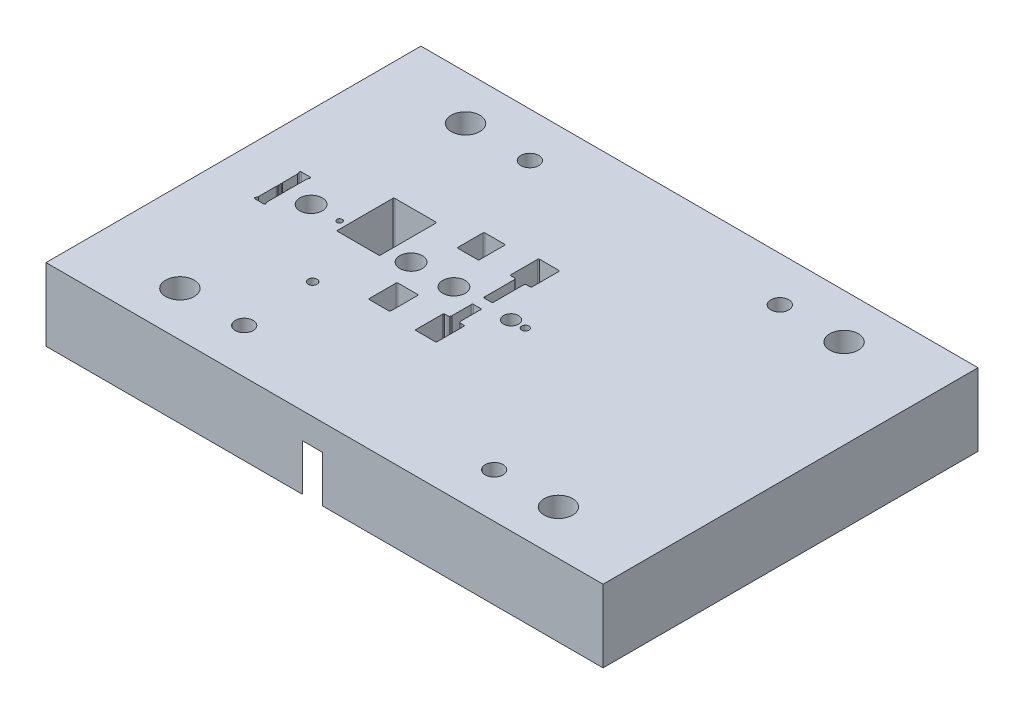
SolidWorks part; units mm, degrees
ref_plane "Front" through (0, 0, 0) normal (0, 0, 1) x (1, 0, 0)
ref_plane "Top" through (0, 0, 0) normal (0, 1, 0) x (1, 0, 0)
ref_plane "Right" through (0, 0, 0) normal (1, 0, 0) x (0, 0, -1)
sketch "Sketch1" plane through (0, 0, 0) normal (0, 0, 1) x (1, 0, 0)
  line L1 (-78, 0) -> (78, 0)
  line L2 (-78, 0) -> (-78, 20.3)
  line L3 (-78, 20.3) -> (78, 20.3)
  line L4 (78, 0) -> (78, 20.3)
  dimension "D1" = 78
  dimension "D2" = 20.3
  dimension "D3" = 78
extrude "Extrude1" add sketch "Sketch1" along normal mid plane 105
hole_wizard "M6 Tapped Hole1" positions "Sketch3" profile "Sketch2" tap size "M6" standard "ISO" end condition through all
sketch "Sketch3" plane through (0, 20.3, 0) normal (0, 1, 0) x (-1, 0, 0)
  point P1 (35, -40)
  point P4 (-35, -40)
  point P13 (-35, 40)
  point P16 (35, 40)
sketch "Sketch2" plane through (-35, 20.3, -40) normal (1, 0, 0) x (0, 0, 1)
  line L0 (0, 0) -> (0, 20.3)
  line L1 (0, 20.3) -> (2.5, 20.3)
  line L2 (2.5, 20.3) -> (2.5, 0)
  line L5 (2.5, 0) -> (0, 0)
  line L11 (0, -6.35) -> (0, 107.95) construction
  dimension "Thru Tap Drill Dia." = 5
  dimension "Thru Tap Drill Depth" = 20.3
cosmetic thread "Hole Thread1" parameters "D2"=6
cosmetic thread "Hole Thread2" parameters "D2"=6
cosmetic thread "Hole Thread5" parameters "D2"=6
cosmetic thread "Hole Thread6" parameters "D2"=6
hole_wizard "Hole1" positions "Sketch5" profile "Sketch4" legacy end condition through all
sketch "Sketch5" plane through (0, 20.3, 0) normal (0, 1, 0) x (-1, 0, 0)
  point P1 (53, -40)
  point P4 (53, 40)
  point P7 (-53, -40)
  point P10 (-53, 40)
sketch "Sketch4" plane through (-53, 20.3, -40) normal (1, 0, 0) x (0, 0, 1)
  line L0 (0, 0) -> (0, 20.3)
  line L1 (0, 20.3) -> (4, 20.3)
  line L2 (4, 20.3) -> (4, 0)
  line L3 (4, 0) -> (0, 0)
  line L4 (0, 110) -> (0, -10) construction
  dimension "Diameter" = 8
  dimension "Depth" = 20.3
hole_wizard "Hole2" positions "Sketch7" profile "Sketch6" legacy
sketch "Sketch7" plane through (0, 0, 0) normal (0, -1, 0) x (1, 0, 0)
  point P0 (14, 14.65)
  point P3 (5, 12.15)
  point P6 (5, -12.1677)
  point P8 (14, -14.65)
  point P11 (35, -12.15)
  point P14 (35, 12.15)
  point P17 (44, 14.65)
  point P20 (44, -14.65)
sketch "Sketch6" plane through (14, 0, 14.65) normal (1, 0, 0) x (0, 0, -1)
  line L0 (0, 0) -> (0, 4.4)
  line L1 (0, 4.4) -> (3.5, 4.4)
  line L2 (3.5, 4.4) -> (3.5, 0)
  line L3 (3.5, 0) -> (0, 0)
  line L4 (0, 110) -> (0, -10) construction
  dimension "Diameter" = 7
  dimension "Depth" = 4.4
sketch "Sketch8" plane through (0, 0, 0) normal (0, -1, 0) x (1, 0, 0)
  line L0 (-78, 52.5) -> (-78, -52.5) construction
  line L1 (-78, 23) -> (-49, 23)
  line L2 (-78, 23) -> (-78, 5)
  line L3 (-78, 5) -> (-49, 5)
  line L4 (-46, 20) -> (-46, 8)
  line L5 (-75.2525, 6) -> (-50.7475, 6) construction
  line L6 (-78, -1) -> (-49, -1)
  line L7 (-78, -1) -> (-78, -21)
  line L8 (-78, -21) -> (-49, -21)
  line L9 (-46, -4) -> (-46, -18)
  line L10 (-78, 22) -> (-48, 22) construction
  line L11 (-76.6263, -2) -> (-49.3737, -2) construction
  line L13 (-78, -20) -> (-48, -20) construction
  line L14 (-48, 11) -> (-48, 22) construction
  arc A0 (-49, -21) -> (-46, -18) centre (-49, -18) ccw
  arc A1 (-49, -1) -> (-46, -4) centre (-49, -4) cw
  arc A2 (-49, 5) -> (-46, 8) centre (-49, 8) ccw
  arc A3 (-49, 23) -> (-46, 20) centre (-49, 20) cw
  dimension "D6" = 3
  dimension "D1" = 1
  dimension "D2" = 1
  dimension "D3" = 1
  dimension "D4" = 1
  dimension "D5" = 2
extrude "Cut-Extrude1" cut sketch "Sketch8" against normal blind 5
sketch "Sketch9" plane through (0, 20.3, 0) normal (0, 1, 0) x (1, 0, 0)
  line L0 (-9.965, 17.15) -> (-9.965, 9.65)
  line L1 (-9.7, 9.385) -> (-8.5894, 9.385)
  line L2 (-8.3917, 9.2771) -> (-8.3123, 9.1537)
  line L3 (-8.275, 9.0266) -> (-8.275, 0.7046)
  line L4 (-18.25, -8.1954) -> (-23.75, -8.1954)
  line L5 (-24, -8.4454) -> (-24, -15.9454)
  line L6 (-23.75, -16.1954) -> (-18.25, -16.1954)
  line L7 (-18, -15.9454) -> (-18, -8.4454)
  line L8 (-18.25, -8.1954) -> (-23.75, -8.1954) construction
  line L9 (-24, -8.4454) -> (-24, -15.9454) construction
  line L10 (-23.75, -16.1954) -> (-18.25, -16.1954) construction
  line L11 (-18, -15.9454) -> (-18, -8.4454) construction
  line L12 (-24, 15.9) -> (-24, 8.9)
  line L13 (-23.75, 8.65) -> (-18.25, 8.65)
  line L14 (-18, 8.9) -> (-18, 15.9)
  line L15 (-18.25, 16.15) -> (-23.75, 16.15)
  line L16 (-24, 15.9) -> (-24, 8.9) construction
  line L17 (-23.75, 8.65) -> (-18.25, 8.65) construction
  line L18 (-18, 8.9) -> (-18, 15.9) construction
  line L19 (-18.25, 16.15) -> (-23.75, 16.15) construction
  line L20 (-33.25, 11.9046) -> (-44.75, 11.9046)
  line L21 (-33, -3.8454) -> (-33, 11.6546)
  line L22 (-44.75, -4.0954) -> (-33.25, -4.0954)
  line L23 (-45, 11.6546) -> (-45, -3.8454)
  line L24 (-33.25, 11.9046) -> (-44.75, 11.9046) construction
  line L25 (-33, -3.8454) -> (-33, 11.6546) construction
  line L26 (-44.75, -4.0954) -> (-33.25, -4.0954) construction
  line L27 (-45, 11.6546) -> (-45, -3.8454) construction
  line L28 (-8.2892, 0.6243) -> (-8.299, 0.5972)
  line L29 (-8.05, 0.2416) -> (-5.95, 0.2416)
  line L30 (-63, -1.2694) -> (-60.1263, -1.2694) construction
  line L31 (-61.75, -6.7884) -> (-61.5151, -7.4339) construction
  line L32 (-64.25, -6.7884) -> (-64.4849, -7.4339) construction
  line L33 (-61.735, -6.7858) -> (-61.501, -7.4288)
  line L34 (-61.75, -7.7844) -> (-64.25, -7.7844)
  line L35 (-64.265, -6.7858) -> (-64.499, -7.4288)
  line L36 (-9, -9.1754) -> (-9.7, -9.1754)
  line L37 (-9.95, -9.4254) -> (-9.95, -16.9254)
  line L38 (-9.7, -17.1754) -> (-4.3, -17.1754)
  line L39 (-4.05, -16.9254) -> (-4.05, -9.4254)
  line L40 (-4.3, -9.1754) -> (-5, -9.1754)
  line L41 (-5.6073, -8.9669) -> (-5.7285, -8.582)
  line L42 (-5.74, -8.5069) -> (-5.74, -3.2709)
  line L43 (-5.7249, -3.1854) -> (-5.7051, -3.1309)
  line L44 (-5.94, -2.7954) -> (-8.06, -2.7954)
  line L45 (-8.2949, -3.1309) -> (-8.2751, -3.1854)
  line L46 (-8.26, -3.2709) -> (-8.26, -8.5069)
  line L47 (-8.2715, -8.582) -> (-8.3927, -8.9669)
  line L48 (-9, -9.1754) -> (-9.7, -9.1754) construction
  line L49 (-9.95, -9.4254) -> (-9.95, -16.9254) construction
  line L50 (-9.7, -17.1754) -> (-4.3, -17.1754) construction
  line L51 (-4.05, -16.9254) -> (-4.05, -9.4254) construction
  line L52 (-4.3, -9.1754) -> (-5, -9.1754) construction
  line L53 (-5.6073, -8.9669) -> (-5.7285, -8.582) construction
  line L54 (-5.74, -8.5069) -> (-5.74, -3.2709) construction
  line L55 (-5.7249, -3.1854) -> (-5.7051, -3.1309) construction
  line L56 (-5.94, -2.7954) -> (-8.06, -2.7954) construction
  line L57 (-8.2949, -3.1309) -> (-8.2751, -3.1854) construction
  line L58 (-8.26, -3.2709) -> (-8.26, -8.5069) construction
  line L59 (-8.2715, -8.582) -> (-8.3927, -8.9669) construction
  line L60 (-9.95, 17.15) -> (-9.95, 9.65)
  line L61 (-9.7, 9.4) -> (-8.5894, 9.4)
  line L62 (-8.3791, 9.2852) -> (-8.2997, 9.1618)
  line L63 (-8.26, 9.0266) -> (-8.26, 0.7046)
  line L64 (-8.2751, 0.6191) -> (-8.2849, 0.5921)
  line L65 (-8.05, 0.2566) -> (-5.95, 0.2566)
  line L66 (-5.7151, 0.5921) -> (-5.7249, 0.6191)
  line L67 (-5.74, 0.7046) -> (-5.74, 9.0266)
  line L68 (-5.7003, 9.1618) -> (-5.6209, 9.2852)
  line L69 (-5.4106, 9.4) -> (-4.3, 9.4)
  line L70 (-4.05, 9.65) -> (-4.05, 17.15)
  line L71 (-4.3, 17.4) -> (-9.7, 17.4)
  line L72 (-9.95, 17.15) -> (-9.95, 9.65) construction
  line L73 (-9.7, 9.4) -> (-8.5894, 9.4) construction
  line L74 (-8.3791, 9.2852) -> (-8.2997, 9.1618) construction
  line L75 (-8.26, 9.0266) -> (-8.26, 0.7046) construction
  line L76 (-8.2751, 0.6191) -> (-8.2849, 0.5921) construction
  line L77 (-8.05, 0.2566) -> (-5.95, 0.2566) construction
  line L78 (-5.7151, 0.5921) -> (-5.7249, 0.6191) construction
  line L79 (-5.74, 0.7046) -> (-5.74, 9.0266) construction
  line L80 (-5.7003, 9.1618) -> (-5.6209, 9.2852) construction
  line L81 (-5.4106, 9.4) -> (-4.3, 9.4) construction
  line L82 (-4.05, 9.65) -> (-4.05, 17.15) construction
  line L83 (-4.3, 17.4) -> (-9.7, 17.4) construction
  line L84 (-64.265, -1.7954) -> (-64.265, -6.7858)
  line L85 (-64.265, 4.247) -> (-64.265, 0.0046)
  line L86 (-64.265, 4.247) -> (-64.499, 4.89)
  line L87 (-64.25, 5.2456) -> (-61.75, 5.2456)
  line L88 (-61.735, 4.247) -> (-61.501, 4.89)
  line L89 (-61.735, 0.0046) -> (-61.735, 4.247)
  line L90 (-5.701, 0.5972) -> (-5.7108, 0.6243)
  line L91 (-5.725, 0.7046) -> (-5.725, 9.0266)
  line L92 (-5.6877, 9.1537) -> (-5.6083, 9.2771)
  line L93 (-5.4106, 9.385) -> (-4.3, 9.385)
  line L94 (-4.035, 9.65) -> (-4.035, 17.15)
  line L95 (-4.3, 17.415) -> (-9.7, 17.415)
  line L96 (-61.735, -6.7858) -> (-61.735, -1.7954)
  line L114 (-64.25, 7.2306) -> (-64.25, 0.0046) construction
  line L115 (-61.75, 0.0046) -> (-61.75, 7.2306) construction
  line L116 (-64.25, -1.7954) -> (-64.25, -9.7694) construction
  line L117 (-61.75, -9.7694) -> (-61.75, -1.7954) construction
  line L118 (-61.75, -7.7694) -> (-64.25, -7.7694) construction
  line L119 (-64.25, 5.2306) -> (-61.75, 5.2306) construction
  line L120 (-64.25, 4.2497) -> (-64.25, 0.0046) construction
  line L121 (-61.75, 0.0046) -> (-61.75, 4.2497) construction
  line L122 (-64.25, -1.7954) -> (-64.25, -6.7884) construction
  line L123 (-61.75, -6.7884) -> (-61.75, -1.7954) construction
  line L124 (-61.75, -7.7694) -> (-64.25, -7.7694) construction
  line L125 (-64.25, 5.2306) -> (-61.75, 5.2306) construction
  line L126 (-64.25, 4.2497) -> (-64.4849, 4.8951) construction
  line L127 (-64.25, 3.4217) -> (-61.75, 3.4217) construction
  line L128 (-63, 3.4217) -> (-63, 4.4835) construction
  line L129 (-61.75, 4.2497) -> (-61.5151, 4.8951) construction
  line L130 (-63, -7.7694) -> (-63, 5.2306) construction
  line L138 (-9, -9.1604) -> (-9.7, -9.1604)
  line L139 (-9.965, -9.4254) -> (-9.965, -16.9254)
  line L140 (-9.7, -17.1904) -> (-4.3, -17.1904)
  line L141 (-4.035, -16.9254) -> (-4.035, -9.4254)
  line L142 (-4.3, -9.1604) -> (-5, -9.1604)
  line L143 (-5.593, -8.9624) -> (-5.7142, -8.5775)
  line L144 (-5.725, -8.5069) -> (-5.725, -3.2709)
  line L145 (-5.7108, -3.1905) -> (-5.691, -3.136)
  line L146 (-5.94, -2.7804) -> (-8.06, -2.7804)
  line L147 (-8.309, -3.136) -> (-8.2892, -3.1905)
  line L148 (-8.275, -3.2709) -> (-8.275, -8.5069)
  line L149 (-8.2858, -8.5775) -> (-8.407, -8.9624)
  line L150 (-24.015, 15.9) -> (-24.015, 8.9)
  line L151 (-23.75, 8.635) -> (-18.25, 8.635)
  line L152 (-17.985, 8.9) -> (-17.985, 15.9)
  line L153 (-18.25, 16.165) -> (-23.75, 16.165)
  line L154 (-18.25, -8.1804) -> (-23.75, -8.1804)
  line L155 (-24.015, -8.4454) -> (-24.015, -15.9454)
  line L156 (-23.75, -16.2104) -> (-18.25, -16.2104)
  line L157 (-17.985, -15.9454) -> (-17.985, -8.4454)
  line L158 (-33.25, 11.9196) -> (-44.75, 11.9196)
  line L159 (-45.015, 11.6546) -> (-45.015, -3.8454)
  line L160 (-44.75, -4.1104) -> (-33.25, -4.1104)
  line L161 (-32.985, -3.8454) -> (-32.985, 11.6546)
  arc A0 (-9.965, 9.65) -> (-9.7, 9.385) centre (-9.7, 9.65) ccw
  arc A1 (-8.3917, 9.2771) -> (-8.5894, 9.385) centre (-8.5894, 9.15) ccw
  arc A2 (-8.275, 9.0266) -> (-8.3123, 9.1537) centre (-8.51, 9.0266) ccw
  arc A3 (-8.2892, 0.6243) -> (-8.275, 0.7046) centre (-8.51, 0.7046) ccw
  arc A4 (-23.75, -8.1954) -> (-24, -8.4454) centre (-23.75, -8.4454) ccw
  arc A5 (-24, -15.9454) -> (-23.75, -16.1954) centre (-23.75, -15.9454) ccw
  arc A6 (-18.25, -16.1954) -> (-18, -15.9454) centre (-18.25, -15.9454) ccw
  arc A7 (-18, -8.4454) -> (-18.25, -8.1954) centre (-18.25, -8.4454) ccw
  arc A8 (-23.75, -8.1954) -> (-24, -8.4454) centre (-23.75, -8.4454) ccw construction
  arc A9 (-24, -15.9454) -> (-23.75, -16.1954) centre (-23.75, -15.9454) ccw construction
  arc A10 (-18.25, -16.1954) -> (-18, -15.9454) centre (-18.25, -15.9454) ccw construction
  arc A11 (-18, -8.4454) -> (-18.25, -8.1954) centre (-18.25, -8.4454) ccw construction
  arc A12 (-24, 8.9) -> (-23.75, 8.65) centre (-23.75, 8.9) ccw
  arc A13 (-18.25, 8.65) -> (-18, 8.9) centre (-18.25, 8.9) ccw
  arc A14 (-18, 15.9) -> (-18.25, 16.15) centre (-18.25, 15.9) ccw
  arc A15 (-23.75, 16.15) -> (-24, 15.9) centre (-23.75, 15.9) ccw
  arc A16 (-24, 8.9) -> (-23.75, 8.65) centre (-23.75, 8.9) ccw construction
  arc A17 (-18.25, 8.65) -> (-18, 8.9) centre (-18.25, 8.9) ccw construction
  arc A18 (-18, 15.9) -> (-18.25, 16.15) centre (-18.25, 15.9) ccw construction
  arc A19 (-23.75, 16.15) -> (-24, 15.9) centre (-23.75, 15.9) ccw construction
  arc A20 (-33, 11.6546) -> (-33.25, 11.9046) centre (-33.25, 11.6546) ccw
  arc A21 (-33.25, -4.0954) -> (-33, -3.8454) centre (-33.25, -3.8454) ccw
  arc A22 (-45, -3.8454) -> (-44.75, -4.0954) centre (-44.75, -3.8454) ccw
  arc A23 (-44.75, 11.9046) -> (-45, 11.6546) centre (-44.75, 11.6546) ccw
  arc A24 (-33, 11.6546) -> (-33.25, 11.9046) centre (-33.25, 11.6546) ccw construction
  arc A25 (-33.25, -4.0954) -> (-33, -3.8454) centre (-33.25, -3.8454) ccw construction
  arc A26 (-45, -3.8454) -> (-44.75, -4.0954) centre (-44.75, -3.8454) ccw construction
  arc A27 (-44.75, 11.9046) -> (-45, 11.6546) centre (-44.75, 11.6546) ccw construction
  arc A28 (-8.299, 0.5972) -> (-8.05, 0.2416) centre (-8.05, 0.5066) ccw
  arc A29 (-5.95, 0.2416) -> (-5.701, 0.5972) centre (-5.95, 0.5066) ccw
  arc A30 (-5.725, 0.7046) -> (-5.7108, 0.6243) centre (-5.49, 0.7046) ccw
  arc A31 (-5.6877, 9.1537) -> (-5.725, 9.0266) centre (-5.49, 9.0266) ccw
  arc A32 (-5.4106, 9.385) -> (-5.6083, 9.2771) centre (-5.4106, 9.15) ccw
  arc A33 (-4.3, 9.385) -> (-4.035, 9.65) centre (-4.3, 9.65) ccw
  arc A34 (-4.035, 17.15) -> (-4.3, 17.415) centre (-4.3, 17.15) ccw
  arc A35 (-9.7, 17.415) -> (-9.965, 17.15) centre (-9.7, 17.15) ccw
  arc A36 (-9.95, 9.65) -> (-9.7, 9.4) centre (-9.7, 9.65) ccw
  arc A37 (-8.3791, 9.2852) -> (-8.5894, 9.4) centre (-8.5894, 9.15) ccw
  arc A38 (-8.26, 9.0266) -> (-8.2997, 9.1618) centre (-8.51, 9.0266) ccw
  arc A39 (-8.2751, 0.6191) -> (-8.26, 0.7046) centre (-8.51, 0.7046) ccw
  arc A40 (-8.5194, -9.0963) -> (-8.4688, -9.0707) centre (-8.5835, -8.9068) ccw
  arc A41 (-9, -9.1754) -> (-8.5194, -9.0963) centre (-9, -7.6754) ccw
  arc A42 (-9.7, -9.1754) -> (-9.95, -9.4254) centre (-9.7, -9.4254) ccw
  arc A43 (-9.95, -16.9254) -> (-9.7, -17.1754) centre (-9.7, -16.9254) ccw
  arc A44 (-4.3, -17.1754) -> (-4.05, -16.9254) centre (-4.3, -16.9254) ccw
  arc A45 (-4.05, -9.4254) -> (-4.3, -9.1754) centre (-4.3, -9.4254) ccw
  arc A46 (-5.4806, -9.0963) -> (-5, -9.1754) centre (-5, -7.6754) ccw
  arc A47 (-5.5312, -9.0707) -> (-5.4806, -9.0963) centre (-5.4165, -8.9068) ccw
  arc A48 (-5.6073, -8.9669) -> (-5.5312, -9.0707) centre (-5.4165, -8.9068) ccw
  arc A49 (-5.74, -8.5069) -> (-5.7285, -8.582) centre (-5.49, -8.5069) ccw
  arc A50 (-5.7249, -3.1854) -> (-5.74, -3.2709) centre (-5.49, -3.2709) ccw
  arc A51 (-5.7051, -3.1309) -> (-5.94, -2.7954) centre (-5.94, -3.0454) ccw
  arc A52 (-8.06, -2.7954) -> (-8.2949, -3.1309) centre (-8.06, -3.0454) ccw
  arc A53 (-8.26, -3.2709) -> (-8.2751, -3.1854) centre (-8.51, -3.2709) ccw
  arc A54 (-8.2715, -8.582) -> (-8.26, -8.5069) centre (-8.51, -8.5069) ccw
  arc A55 (-8.4688, -9.0707) -> (-8.3927, -8.9669) centre (-8.5835, -8.9068) ccw
  arc A56 (-8.5194, -9.0963) -> (-8.4688, -9.0707) centre (-8.5835, -8.9068) ccw construction
  arc A57 (-9, -9.1754) -> (-8.5194, -9.0963) centre (-9, -7.6754) ccw construction
  arc A58 (-9.7, -9.1754) -> (-9.95, -9.4254) centre (-9.7, -9.4254) ccw construction
  arc A59 (-9.95, -16.9254) -> (-9.7, -17.1754) centre (-9.7, -16.9254) ccw construction
  arc A60 (-4.3, -17.1754) -> (-4.05, -16.9254) centre (-4.3, -16.9254) ccw construction
  arc A61 (-4.05, -9.4254) -> (-4.3, -9.1754) centre (-4.3, -9.4254) ccw construction
  arc A62 (-5.4806, -9.0963) -> (-5, -9.1754) centre (-5, -7.6754) ccw construction
  arc A63 (-5.5312, -9.0707) -> (-5.4806, -9.0963) centre (-5.4165, -8.9068) ccw construction
  arc A64 (-5.6073, -8.9669) -> (-5.5312, -9.0707) centre (-5.4165, -8.9068) ccw construction
  arc A65 (-5.74, -8.5069) -> (-5.7285, -8.582) centre (-5.49, -8.5069) ccw construction
  arc A66 (-5.7249, -3.1854) -> (-5.74, -3.2709) centre (-5.49, -3.2709) ccw construction
  arc A67 (-5.7051, -3.1309) -> (-5.94, -2.7954) centre (-5.94, -3.0454) ccw construction
  arc A68 (-8.06, -2.7954) -> (-8.2949, -3.1309) centre (-8.06, -3.0454) ccw construction
  arc A69 (-8.26, -3.2709) -> (-8.2751, -3.1854) centre (-8.51, -3.2709) ccw construction
  arc A70 (-8.2715, -8.582) -> (-8.26, -8.5069) centre (-8.51, -8.5069) ccw construction
  arc A71 (-8.4688, -9.0707) -> (-8.3927, -8.9669) centre (-8.5835, -8.9068) ccw construction
  arc A72 (-8.2849, 0.5921) -> (-8.05, 0.2566) centre (-8.05, 0.5066) ccw
  arc A73 (-5.95, 0.2566) -> (-5.7151, 0.5921) centre (-5.95, 0.5066) ccw
  arc A74 (-5.74, 0.7046) -> (-5.7249, 0.6191) centre (-5.49, 0.7046) ccw
  arc A75 (-5.7003, 9.1618) -> (-5.74, 9.0266) centre (-5.49, 9.0266) ccw
  arc A76 (-5.4106, 9.4) -> (-5.6209, 9.2852) centre (-5.4106, 9.15) ccw
  arc A77 (-4.3, 9.4) -> (-4.05, 9.65) centre (-4.3, 9.65) ccw
  arc A78 (-4.05, 17.15) -> (-4.3, 17.4) centre (-4.3, 17.15) ccw
  arc A79 (-9.7, 17.4) -> (-9.95, 17.15) centre (-9.7, 17.15) ccw
  arc A80 (-9.95, 9.65) -> (-9.7, 9.4) centre (-9.7, 9.65) ccw construction
  arc A81 (-8.3791, 9.2852) -> (-8.5894, 9.4) centre (-8.5894, 9.15) ccw construction
  arc A82 (-8.26, 9.0266) -> (-8.2997, 9.1618) centre (-8.51, 9.0266) ccw construction
  arc A83 (-8.2751, 0.6191) -> (-8.26, 0.7046) centre (-8.51, 0.7046) ccw construction
  arc A84 (-8.2849, 0.5921) -> (-8.05, 0.2566) centre (-8.05, 0.5066) ccw construction
  arc A85 (-5.95, 0.2566) -> (-5.7151, 0.5921) centre (-5.95, 0.5066) ccw construction
  arc A86 (-5.74, 0.7046) -> (-5.7249, 0.6191) centre (-5.49, 0.7046) ccw construction
  arc A87 (-5.7003, 9.1618) -> (-5.74, 9.0266) centre (-5.49, 9.0266) ccw construction
  arc A88 (-5.4106, 9.4) -> (-5.6209, 9.2852) centre (-5.4106, 9.15) ccw construction
  arc A89 (-4.3, 9.4) -> (-4.05, 9.65) centre (-4.3, 9.65) ccw construction
  arc A90 (-4.05, 17.15) -> (-4.3, 17.4) centre (-4.3, 17.15) ccw construction
  arc A91 (-9.7, 17.4) -> (-9.95, 17.15) centre (-9.7, 17.15) ccw construction
  arc A92 (-61.5151, -7.4339) -> (-61.75, -7.7694) centre (-61.75, -7.5194) cw construction
  arc A93 (-64.4849, -7.4339) -> (-64.25, -7.7694) centre (-64.25, -7.5194) ccw construction
  arc A94 (-61.501, -7.4288) -> (-61.75, -7.7844) centre (-61.75, -7.5194) cw
  arc A95 (-64.499, -7.4288) -> (-64.25, -7.7844) centre (-64.25, -7.5194) ccw
  arc A96 (-64.212, -1.6364) -> (-64.265, -1.7954) centre (-64, -1.7954) ccw
  arc A97 (-64.212, -1.6364) -> (-64.212, -1.3544) centre (-64.4, -1.4954) ccw
  arc A98 (-64.212, -1.0364) -> (-64.212, -1.3544) centre (-64, -1.1954) ccw
  arc A99 (-64.212, -1.0364) -> (-64.212, -0.7544) centre (-64.4, -0.8954) ccw
  arc A100 (-64.212, -0.4364) -> (-64.212, -0.7544) centre (-64, -0.5954) ccw
  arc A101 (-64.212, -0.4364) -> (-64.212, -0.1544) centre (-64.4, -0.2954) ccw
  arc A102 (-64.265, 0.0046) -> (-64.212, -0.1544) centre (-64, 0.0046) ccw
  arc A103 (-64.499, 4.89) -> (-64.25, 5.2456) centre (-64.25, 4.9806) cw
  arc A104 (-61.501, 4.89) -> (-61.75, 5.2456) centre (-61.75, 4.9806) ccw
  arc A105 (-61.788, -0.1544) -> (-61.735, 0.0046) centre (-62, 0.0046) ccw
  arc A106 (-61.788, -0.1544) -> (-61.788, -0.4364) centre (-61.6, -0.2954) ccw
  arc A107 (-61.788, -0.7544) -> (-61.788, -0.4364) centre (-62, -0.5954) ccw
  arc A108 (-61.788, -0.7544) -> (-61.788, -1.0364) centre (-61.6, -0.8954) ccw
  arc A109 (-61.788, -1.3544) -> (-61.788, -1.0364) centre (-62, -1.1954) ccw
  arc A110 (-61.788, -1.3544) -> (-61.788, -1.6364) centre (-61.6, -1.4954) ccw
  arc A111 (-61.735, -1.7954) -> (-61.788, -1.6364) centre (-62, -1.7954) ccw
  arc A132 (-61.8, -0.1454) -> (-61.75, 0.0046) centre (-62, 0.0046) ccw construction
  arc A133 (-61.8, -0.1454) -> (-61.8, -0.4454) centre (-61.6, -0.2954) ccw construction
  arc A134 (-61.8, -0.7454) -> (-61.8, -0.4454) centre (-62, -0.5954) ccw construction
  arc A135 (-61.8, -0.7454) -> (-61.8, -1.0454) centre (-61.6, -0.8954) ccw construction
  arc A136 (-61.8, -1.3454) -> (-61.8, -1.0454) centre (-62, -1.1954) ccw construction
  arc A137 (-61.8, -1.3454) -> (-61.8, -1.6454) centre (-61.6, -1.4954) ccw construction
  arc A138 (-61.75, -1.7954) -> (-61.8, -1.6454) centre (-62, -1.7954) ccw construction
  arc A139 (-61.8, -0.1454) -> (-61.75, 0.0046) centre (-62, 0.0046) ccw construction
  arc A140 (-61.8, -0.1454) -> (-61.8, -0.4454) centre (-61.6, -0.2954) ccw construction
  arc A141 (-61.8, -0.7454) -> (-61.8, -0.4454) centre (-62, -0.5954) ccw construction
  arc A142 (-61.8, -0.7454) -> (-61.8, -1.0454) centre (-61.6, -0.8954) ccw construction
  arc A143 (-61.8, -1.3454) -> (-61.8, -1.0454) centre (-62, -1.1954) ccw construction
  arc A144 (-61.8, -1.3454) -> (-61.8, -1.6454) centre (-61.6, -1.4954) ccw construction
  arc A145 (-61.75, -1.7954) -> (-61.8, -1.6454) centre (-62, -1.7954) ccw construction
  arc A146 (-64.25, 0.0046) -> (-64.2, -0.1454) centre (-64, 0.0046) ccw construction
  arc A147 (-64.2, -0.4454) -> (-64.2, -0.1454) centre (-64.4, -0.2954) ccw construction
  arc A148 (-64.2, -0.4454) -> (-64.2, -0.7454) centre (-64, -0.5954) ccw construction
  arc A149 (-64.2, -1.0454) -> (-64.2, -0.7454) centre (-64.4, -0.8954) ccw construction
  arc A150 (-64.2, -1.0454) -> (-64.2, -1.3454) centre (-64, -1.1954) ccw construction
  arc A151 (-64.2, -1.6454) -> (-64.2, -1.3454) centre (-64.4, -1.4954) ccw construction
  arc A152 (-64.2, -1.6454) -> (-64.25, -1.7954) centre (-64, -1.7954) ccw construction
  arc A153 (-64.25, 0.0046) -> (-64.2, -0.1454) centre (-64, 0.0046) ccw construction
  arc A154 (-64.2, -0.4454) -> (-64.2, -0.1454) centre (-64.4, -0.2954) ccw construction
  arc A155 (-64.2, -0.4454) -> (-64.2, -0.7454) centre (-64, -0.5954) ccw construction
  arc A156 (-64.2, -1.0454) -> (-64.2, -0.7454) centre (-64.4, -0.8954) ccw construction
  arc A157 (-64.2, -1.0454) -> (-64.2, -1.3454) centre (-64, -1.1954) ccw construction
  arc A158 (-64.2, -1.6454) -> (-64.2, -1.3454) centre (-64.4, -1.4954) ccw construction
  arc A159 (-64.2, -1.6454) -> (-64.25, -1.7954) centre (-64, -1.7954) ccw construction
  arc A160 (-64.4849, 4.8951) -> (-64.25, 5.2306) centre (-64.25, 4.9806) cw construction
  arc A161 (-61.5151, 4.8951) -> (-61.75, 5.2306) centre (-61.75, 4.9806) ccw construction
  arc A186 (-9.7, -9.1604) -> (-9.965, -9.4254) centre (-9.7, -9.4254) ccw
  arc A187 (-9.965, -16.9254) -> (-9.7, -17.1904) centre (-9.7, -16.9254) ccw
  arc A188 (-4.3, -17.1904) -> (-4.035, -16.9254) centre (-4.3, -16.9254) ccw
  arc A189 (-4.035, -9.4254) -> (-4.3, -9.1604) centre (-4.3, -9.4254) ccw
  arc A190 (-5.4758, -9.0821) -> (-5, -9.1604) centre (-5, -7.6754) ccw
  arc A191 (-5.5226, -9.0584) -> (-5.4758, -9.0821) centre (-5.4165, -8.9068) ccw
  arc A192 (-5.593, -8.9624) -> (-5.5226, -9.0584) centre (-5.4165, -8.9068) ccw
  arc A193 (-5.725, -8.5069) -> (-5.7142, -8.5775) centre (-5.49, -8.5069) ccw
  arc A194 (-5.7108, -3.1905) -> (-5.725, -3.2709) centre (-5.49, -3.2709) ccw
  arc A195 (-5.691, -3.136) -> (-5.94, -2.7804) centre (-5.94, -3.0454) ccw
  arc A196 (-8.06, -2.7804) -> (-8.309, -3.136) centre (-8.06, -3.0454) ccw
  arc A197 (-8.275, -3.2709) -> (-8.2892, -3.1905) centre (-8.51, -3.2709) ccw
  arc A198 (-8.2858, -8.5775) -> (-8.275, -8.5069) centre (-8.51, -8.5069) ccw
  arc A199 (-8.4774, -9.0584) -> (-8.407, -8.9624) centre (-8.5835, -8.9068) ccw
  arc A200 (-8.5242, -9.0821) -> (-8.4774, -9.0584) centre (-8.5835, -8.9068) ccw
  arc A201 (-9, -9.1604) -> (-8.5242, -9.0821) centre (-9, -7.6754) ccw
  arc A202 (-24.015, 8.9) -> (-23.75, 8.635) centre (-23.75, 8.9) ccw
  arc A203 (-18.25, 8.635) -> (-17.985, 8.9) centre (-18.25, 8.9) ccw
  arc A204 (-17.985, 15.9) -> (-18.25, 16.165) centre (-18.25, 15.9) ccw
  arc A205 (-23.75, 16.165) -> (-24.015, 15.9) centre (-23.75, 15.9) ccw
  arc A206 (-23.75, -8.1804) -> (-24.015, -8.4454) centre (-23.75, -8.4454) ccw
  arc A207 (-24.015, -15.9454) -> (-23.75, -16.2104) centre (-23.75, -15.9454) ccw
  arc A208 (-18.25, -16.2104) -> (-17.985, -15.9454) centre (-18.25, -15.9454) ccw
  arc A209 (-17.985, -8.4454) -> (-18.25, -8.1804) centre (-18.25, -8.4454) ccw
  arc A210 (-44.75, 11.9196) -> (-45.015, 11.6546) centre (-44.75, 11.6546) ccw
  arc A211 (-45.015, -3.8454) -> (-44.75, -4.1104) centre (-44.75, -3.8454) ccw
  arc A212 (-33.25, -4.1104) -> (-32.985, -3.8454) centre (-33.25, -3.8454) ccw
  arc A213 (-32.985, 11.6546) -> (-33.25, 11.9196) centre (-33.25, 11.6546) ccw
  dimension "D12" = 0.25
  dimension "D6" = 20
  dimension "D1" = 0
  dimension "D2" = 0
  dimension "D3" = 0
  dimension "D4" = 0
  dimension "D5" = 0
  dimension "D7" = 0.015
  dimension "D8" = 0.015
  dimension "D9" = 0.015
  dimension "D10" = 0.015
  dimension "D11" = 0.015
  dimension "D13" = 0.015
extrude "Cut-Extrude2" cut sketch "Sketch9" against normal through all
hole_wizard "Hole3" positions "Sketch11" profile "Sketch10" legacy
sketch "Sketch11" plane through (0, 20.3, 0) normal (0, 1, 0) x (1, 0, 0)
  point P0 (1, -1.2694)
  point P3 (-15, -1.2694)
  point P6 (-27, -1.2694)
  point P9 (-55, -1.2694)
sketch "Sketch10" plane through (1, 20.3, 1.2694) normal (1, 0, 0) x (0, 0, 1)
  line L0 (0, 0) -> (0, 100)
  line L1 (0, 100) -> (1, 100)
  line L2 (1, 100) -> (1, 11.0392)
  line L3 (1, 11.0392) -> (1.6, 10)
  line L4 (1.6, 10) -> (1.6, 0)
  line L5 (1.6, 0) -> (0, 0)
  line L6 (0, -6.13) -> (0, 109.2824) construction
  line L7 (-1, 11.0392) -> (-1.6, 10) construction
  line L8 (0, 100) -> (-1, 100) construction
  dimension "Diameter" = 2
  dimension "Depth" = 100
  dimension "C-Drill Diameter" = 3.2
  dimension "C-Drill Depth" = 10
  dimension "C-Drill Angle" = 60
hole_wizard "Hole4" positions "Sketch13" profile "Sketch12" legacy
sketch "Sketch13" plane through (0, 20.3, 0) normal (0, 1, 0) x (1, 0, 0)
  point P0 (-15, -1.2694)
  point P3 (-27, -1.2694)
  point P6 (-55, -1.2694)
sketch "Sketch12" plane through (-15, 20.3, 1.2694) normal (1, 0, 0) x (0, 0, 1)
  line L0 (0, 0) -> (0, 10)
  line L1 (0, 10) -> (3.15, 10)
  line L2 (3.15, 10) -> (3.15, 0)
  line L3 (3.15, 0) -> (0, 0)
  line L4 (0, 110) -> (0, -10) construction
  dimension "Diameter" = 6.3
  dimension "Depth" = 10
hole_wizard "Hole6" positions "Sketch15" profile "Sketch14" legacy
sketch "Sketch15" plane through (0, 20.3, 0) normal (0, 1, 0) x (1, 0, 0)
  point P1 (1, -1.2694)
sketch "Sketch14" plane through (1, 20.3, 1.2694) normal (1, 0, 0) x (0, 0, 1)
  line L0 (0, 0) -> (0, 9.999)
  line L1 (0, 9.999) -> (2.1, 9.999)
  line L2 (2.1, 9.999) -> (2.1, 0)
  line L3 (2.1, 0) -> (0, 0)
  line L4 (0, 110) -> (0, -10) construction
  dimension "Diameter" = 4.2
  dimension "Depth" = 9.999
hole_wizard "Hole7" positions "Sketch17" profile "Sketch16" legacy end condition through all
sketch "Sketch17" plane through (0, 20.3, 0) normal (0, 1, 0) x (1, 0, 0)
  point P0 (5, -1.2694)
sketch "Sketch16" plane through (5, 20.3, 1.2694) normal (1, 0, 0) x (0, 0, 1)
  line L0 (0, 0) -> (0, 20.3)
  line L1 (0, 20.3) -> (1.015, 20.3)
  line L2 (1.015, 20.3) -> (1.015, 0)
  line L3 (1.015, 0) -> (0, 0)
  line L4 (0, 110) -> (0, -10) construction
  dimension "Diameter" = 2.03
  dimension "Depth" = 20.3
hole_wizard "Hole8" positions "Sketch19" profile "Sketch18" legacy end condition through all
sketch "Sketch19" plane through (0, 20.3, 0) normal (0, 1, 0) x (1, 0, 0)
  point P0 (-47, -1.2694)
sketch "Sketch18" plane through (-47, 20.3, 1.2694) normal (1, 0, 0) x (0, 0, 1)
  line L0 (0, 0) -> (0, 20.7506)
  line L1 (0, 20.7506) -> (0.75, 20.3)
  line L2 (0.75, 20.3) -> (0.75, 0)
  line L4 (0.75, 0) -> (0, 0)
  line L6 (0, 20.7506) -> (-0.75, 20.3) construction
  line L7 (0, -4.2442) -> (0, 117.3081) construction
  dimension "Diameter" = 1.5
  dimension "Depth" = 20.3
  dimension "Drill Angle" = 118
ref_plane "Plane1" through (78, 0, -52.5) normal (1, 0, 0) x (0, 0, -1)
sketch "Sketch21" plane through (0, 0, 0) normal (0, -1, 0) x (1, 0, 0)
  line L0 (-52.6533, 7.4489) -> (-26.8439, 33.2583) construction
  line L1 (-24.5391, 34.1347) -> (-3.1635, 55.5103) construction
  line L2 (-3.1635, 55.5103) -> (-0.335, 52.6819) construction
  line L3 (-0.335, 52.6819) -> (-21.7106, 31.3063) construction
  line L4 (-48.3965, 3.1921) -> (-22.5871, 29.0015) construction
  line L5 (-52.6533, 7.4489) -> (-26.8439, 33.2583)
  line L6 (-24.5391, 34.1347) -> (-3.1635, 55.5103)
  line L7 (-3.1635, 55.5103) -> (-0.335, 52.6819)
  line L8 (-0.335, 52.6819) -> (-21.7106, 31.3063)
  line L9 (-48.3965, 3.1921) -> (-22.5871, 29.0015)
  arc A0 (-24.5391, 34.1347) -> (-26.8439, 33.2583) centre (-24.7155, 31.1299) ccw construction
  arc A1 (-22.5871, 29.0015) -> (-21.7106, 31.3063) centre (-24.7155, 31.1299) ccw construction
  arc A2 (-52.6533, 7.4489) -> (-48.3965, 3.1921) centre (-50.5249, 5.3205) ccw construction
  arc A3 (-24.5391, 34.1347) -> (-26.8439, 33.2583) centre (-24.7155, 31.1299) ccw
  arc A4 (-22.5871, 29.0015) -> (-21.7106, 31.3063) centre (-24.7155, 31.1299) ccw
  arc A5 (-52.6533, 7.4489) -> (-48.3965, 3.1921) centre (-50.5249, 5.3205) ccw
extrude "Cut-Extrude3" cut sketch "Sketch21" against normal blind 13
sketch "Sketch23" plane through (0, 0, 0) normal (0, -1, 0) x (1, 0, 0)
  line L0 (-49, 23) -> (-37.1021, 23)
  line L1 (-26.8439, 33.2583) -> (-52.6533, 7.4489) construction
  line L2 (-37.1021, 23) -> (-46, 14.1021)
  line L3 (-46, 14.1021) -> (-49, 23)
extrude "Cut-Extrude4" cut sketch "Sketch23" against normal up to surface (5 mm away) up to face at (-60.4552, 5, 10.1599)
hole_wizard "M3 Tapped Hole1" positions "Sketch24" profile "Sketch25" tap size "M3" standard "ISO"
sketch "Sketch24" plane through (0, 13, 0) normal (0, -1, 0) x (-1, 0, 0)
  point P0 (36.0292, -19.8162)
sketch "Sketch25" plane through (-36.0292, 13, 19.8162) normal (1, 0, 0) x (0, 0, -1)
  line L0 (0, 0) -> (0, 8.2511)
  line L1 (0, 8.2511) -> (1.25, 7.5)
  line L2 (1.25, 7.5) -> (1.25, 0)
  line L5 (1.25, 0) -> (0, 0)
  line L10 (0, 8.2511) -> (-1.25, 7.5) construction
  line L11 (0, -6.35) -> (0, 107.95) construction
  dimension "Tap Drill Dia." = 2.5
  dimension "Tap Drill Depth" = 7.5
  dimension "Drill Angle" = 118
cosmetic thread "Hole Thread7" parameters "D1"=6, "D2"=3
equation "\"¸20\"=24.0852"
